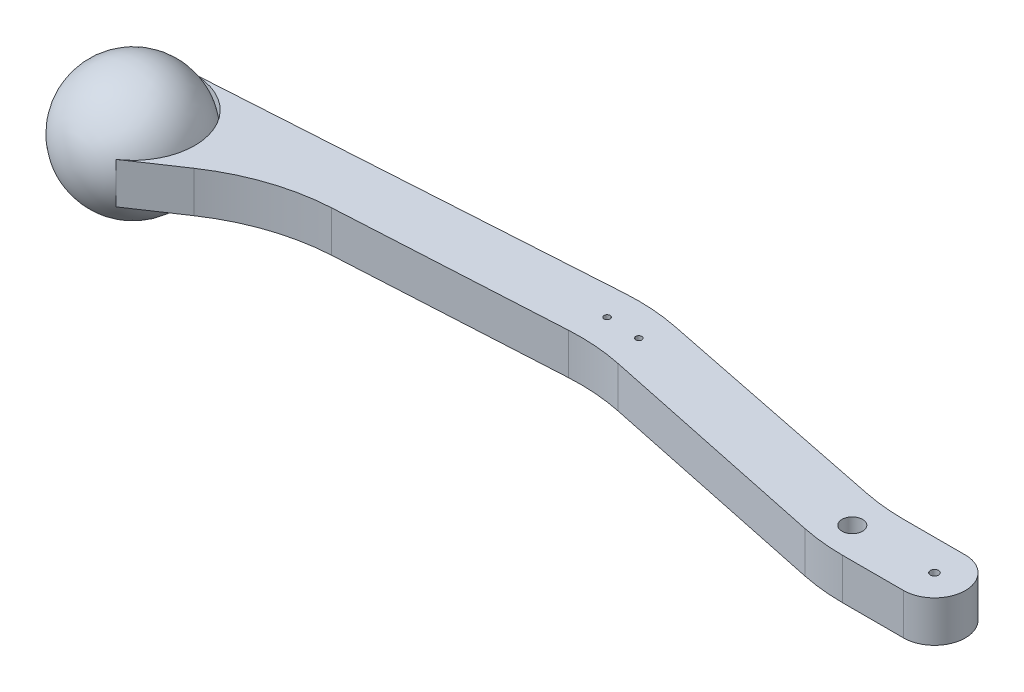
SolidWorks part; units mm, degrees
ref_plane "Front Plane" through (0, 0, 0) normal (0, 0, 1) x (1, 0, 0)
ref_plane "Top Plane" through (0, 0, 0) normal (0, 1, 0) x (1, 0, 0)
ref_plane "Right Plane" through (0, 0, 0) normal (1, 0, 0) x (0, 0, -1)
sketch "Sketch1" plane through (0, 0, 0) normal (0, 1, 0) x (1, 0, 0)
  line L0 (0, 0) -> (-350, 0) construction
  line L1 (0, 0) -> (40, 0) construction
  line L2 (0, 15) -> (40, 15)
  line L3 (0, -15) -> (40, -15)
  line L4 (-351.8754, 29.9413) -> (-333.2857, -24.9125) construction
  line L5 (-139.7849, 43.2259) -> (-4217.6379, -212.1962)
  line L6 (0, 15) -> (-4004.6012, 823.6244)
  line L7 (0, 15) -> (-5.9197, -13.7825) construction
  line L8 (-4217.6379, -212.1962) -> (-138.0533, 13.889)
  line L9 (-4004.6012, 823.6244) -> (-5.9197, -13.7825)
  line L10 (-333.2857, -24.9125) -> (-287.8235, 5.5889)
  line L11 (-5.9197, -13.7825) -> (0, -15)
  circle A0 centre (0, 0) radius 5
  circle A1 centre (-350, 0) radius 30
  circle A2 centre (40, 0) radius 2
  circle A3 centre (0, 0) radius 15
  circle A4 centre (40, 0) radius 15
  dimension "D1" = 10
  dimension "D4" = 4
  dimension "D5" = 60
  dimension "D6" = 30
  dimension "D7" = 165
  dimension "D2" = 350
  dimension "D3" = 40
  dimension "D8" = 165
  dimension "D9" = 135
  dimension "D10" = 150
extrude "Boss-Extrude1" add sketch "Sketch1" along normal blind 10 and the other way blind 10 contours L8 A1 | A1 L8 | A1 L8 L9 L5 | A1 L10 L8 | A3 L6 L5 L9 | A3 A0 | A4 L2 A3 L3 | A4 A2 region at (-104.3815, 0, -20.1768) region at (20, 0, 0) region at (10.3066, 0, -10.3066) region at (50.3066, 0, -10.3066) region at (-256.3648, 0, -20.0554) region at (-350.7689, 0, -13.8751) region at (-310.7553, 0, 3.5404) region at (-349.359, 0, 11.5664)
fillet "Fillet1" radius 100 5 edges at (0, 0, -15) (-139.7849, 0, -43.2259) (-138.0533, 0, -13.889) (-287.8235, 0, -5.5889) (0, 0, 15)
sketch "Sketch2" plane through (0, 10, 0) normal (0, 1, 0) x (1, 0, 0)
  circle A0 centre (-147.3362, 28.0506) radius 1.5
  circle A1 centre (-130.7919, 26.9057) radius 1.5
  circle A2 centre (-364.7467, 9.4158) radius 1.5
  circle A3 centre (-348.0325, -15.4967) radius 1.5
extrude "Cut-Extrude1" cut sketch "Sketch2" against normal blind 10
sketch "Sketch3" plane through (0, 0, 0) normal (0, 1, 0) x (1, 0, 0)
  circle A0 centre (-350, 0) radius 30
extrude "Cut-Extrude2" cut sketch "Sketch3" against normal blind 10 and the other way blind 10
sketch "Sketch4" plane through (0, 0, 0) normal (0, 1, 0) x (1, 0, 0)
  line L0 (-350, 30) -> (-350, -30)
  arc A3 (-350, 30) -> (-350, -30) centre (-350, 0) ccw
  point P1 (0, 0)
  point P2 (0, 0)
revolve "Revolve6" add sketch "Sketch4" angle 360 about L0
